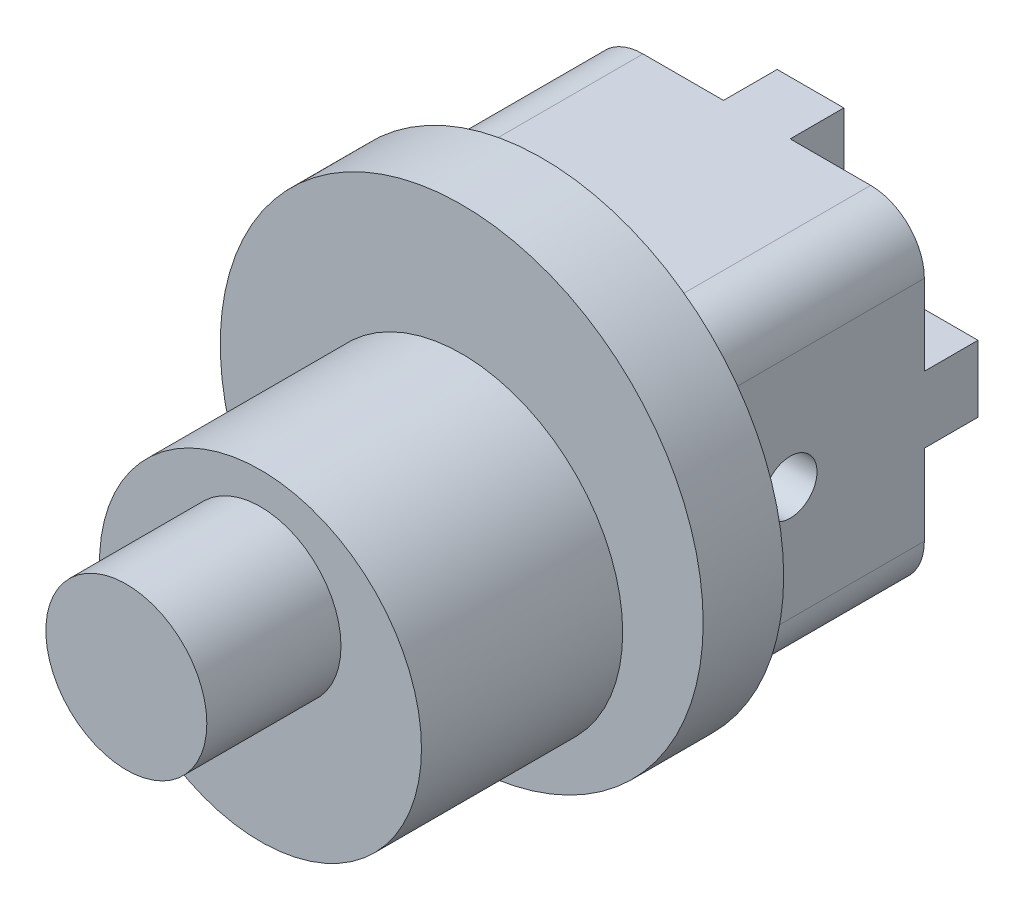
SolidWorks part; units mm, degrees
material "ABS PC"
ref_plane "Front Plane" through (0, 0, 0) normal (0, 0, 1) x (1, 0, 0)
ref_plane "Top Plane" through (0, 0, 0) normal (0, 1, 0) x (1, 0, 0)
ref_plane "Right Plane" through (0, 0, 0) normal (1, 0, 0) x (0, 0, -1)
sketch "Sketch1" plane through (0, 0, 0) normal (0, 0, 1) x (1, 0, 0)
  line L0 (4.2426, 6.2426) -> (-4.2426, 6.2426)
  line L1 (6.2426, 4.2426) -> (6.2426, -4.2426)
  line L2 (4.2426, -6.2426) -> (-4.2426, -6.2426)
  line L3 (-6.2426, 4.2426) -> (-6.2426, -4.2426)
  line L4 (2.2426, 4.2426) -> (2.2426, 6.2426)
  line L5 (4.2426, 2.2426) -> (6.2426, 2.2426)
  line L6 (4.2426, -2.2426) -> (6.2426, -2.2426)
  line L7 (2.2426, -4.2426) -> (2.2426, -6.2426)
  line L8 (-2.2426, -4.2426) -> (-2.2426, -6.2426)
  line L9 (-4.2426, -2.2426) -> (-6.2426, -2.2426)
  line L10 (-4.2426, 2.2426) -> (-6.2426, 2.2426)
  line L11 (-2.2426, 4.2426) -> (-2.2426, 6.2426)
  line L12 (1.2426, 4.2426) -> (1.2426, 6.2426)
  line L13 (4.2426, 1.2426) -> (6.2426, 1.2426)
  line L14 (4.2426, -1.2426) -> (6.2426, -1.2426)
  line L15 (1.2426, -4.2426) -> (1.2426, -6.2426)
  line L16 (-1.2426, -4.2426) -> (-1.2426, -6.2426)
  line L17 (-4.2426, -1.2426) -> (-6.2426, -1.2426)
  line L18 (-4.2426, 1.2426) -> (-6.2426, 1.2426)
  line L19 (-1.2426, 4.2426) -> (-1.2426, 6.2426)
  circle A0 centre (-4.2426, 4.2426) radius 2
  circle A4 centre (4.2426, 4.2426) radius 2
  circle A5 centre (4.2426, -4.2426) radius 2
  circle A6 centre (-4.2426, -4.2426) radius 2
  arc A7 (1.2426, 4.2426) -> (4.2426, 1.2426) centre (4.2426, 4.2426) ccw
  arc A8 (4.2426, -1.2426) -> (1.2426, -4.2426) centre (4.2426, -4.2426) ccw
  arc A9 (-1.2426, -4.2426) -> (-4.2426, -1.2426) centre (-4.2426, -4.2426) ccw
  arc A10 (-4.2426, 1.2426) -> (-1.2426, 4.2426) centre (-4.2426, 4.2426) ccw
  point P13 (0, 0)
  point P55 (0, 0)
  dimension "D1" = 4
  dimension "D3" = 4
  dimension "D2" = 4
sketch "Sketch3" plane through (0, 0, 10) normal (0, 0, 1) x (1, 0, 0)
  circle A0 centre (0, 0) radius 9
  dimension "D1" = 18
extrude "Boss-Extrude3" add sketch "Sketch3" along normal blind 3
sketch "Sketch4" plane through (0, 0, 13) normal (0, 0, 1) x (1, 0, 0)
  circle A0 centre (0, -1.812) radius 6
  dimension "D1" = 12
  dimension "D2" = 1.812
extrude "Boss-Extrude4" add sketch "Sketch4" along normal blind 7.5
sketch "Sketch5" plane through (0, 0, 20.5) normal (0, 0, 1) x (1, 0, 0)
  circle A0 centre (0, 0) radius 3
  dimension "D1" = 6
extrude "Boss-Extrude5" add sketch "Sketch5" along normal blind 5
extrude "Boss-Extrude8" add sketch "Sketch1" along normal blind 2 separate body contours A10 L18 L3 L17 A9 L16 L2 L15 A8 L14 L1 L13 A7 L12 L0 L19 region at (0, 0, 0)
extrude "Boss-Extrude9" add sketch "Sketch1<7>" along normal blind 8 from offset 2 contours A10 L18 L3 L17 A9 L16 L2 L15 A8 L14 L1 L13 A7 L12 L0 L19 | L18 A10 L19 L0 L11 A0 L10 L3 | L12 A7 L13 L1 L5 A4 L4 L0 | L14 A8 L15 L2 L7 A5 L6 L1 | L16 A9 L17 L3 L9 A6 L8 L2 | A6 L9 L3 | A6 | A6 L2 L8 | A5 L7 L2 | A5 | A5 L1 L6 | A4 | A4 L5 L1 | A4 L0 L4 | A0 L11 L0 | A0 | A0 L3 L10 | A4 region at (2.6894, 5.7959, 0) region at (4.2426, 4.2426, 0) region at (2.1719, 5.2426, 0) region at (5.7959, 2.6894, 0) region at (0, 0, 0) region at (-1.3134, 5.2426, 0) region at (-2.6894, 5.7959, 0) region at (6.1719, -1.7426, 0) region at (-4.2426, 4.2426, 0) region at (5.7959, -2.6894, 0) region at (-5.7959, 2.6894, 0) region at (4.2426, -4.2426, 0) region at (-5.2426, -1.3134, 0) region at (2.6894, -5.7959, 0) region at (-5.7959, -2.6894, 0) region at (-4.2426, -4.2426, 0) region at (-2.6894, -5.7959, 0)
sketch "Sketch1<7>" plane through (0, 0, 0) normal (0, 0, 1) x (1, 0, 0) same geometry as "Sketch1"
sketch "Sketch6" plane through (6.2426, 0, 0) normal (1, 0, 0) x (0, 0, -1)
  line L0 (-10, 4.2426) -> (-10, -4.2426) construction
  circle A0 centre (-7, 0) radius 1
  dimension "D1" = 2
  dimension "D2" = 3
extrude "Cut-Extrude1" cut sketch "Sketch6" against normal blind 15
